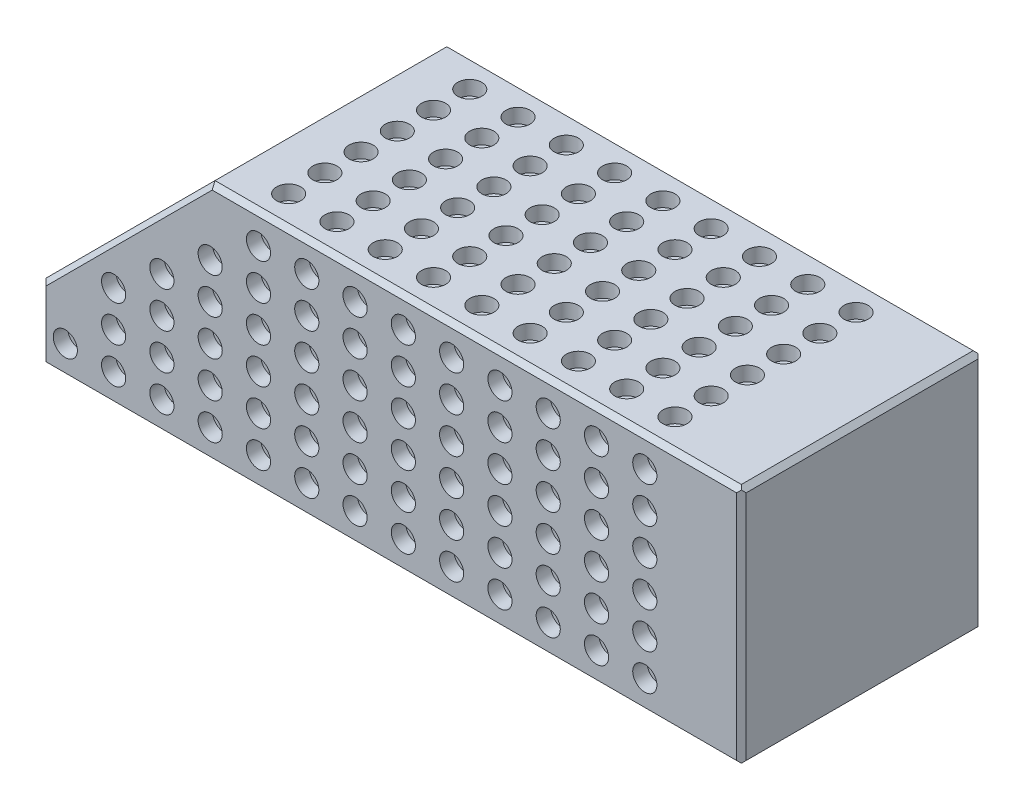
SolidWorks part; units mm, degrees
material "K110"
ref_plane "Front Plane" through (0, 0, 0) normal (0, 0, 1) x (1, 0, 0)
ref_plane "Top Plane" through (0, 0, 0) normal (0, 1, 0) x (1, 0, 0)
ref_plane "Right Plane" through (0, 0, 0) normal (1, 0, 0) x (0, 0, -1)
sketch "Sketch1" plane through (0, 0, 0) normal (0, 0, 1) x (1, 0, 0)
  line L1 (-72.5, -25) -> (72.5, -25)
  line L2 (-72.5, -25) -> (-72.5, 25)
  line L3 (-72.5, 25) -> (72.5, 25)
  line L4 (72.5, -25) -> (72.5, 25)
  line L5 (-72.5, -25) -> (72.5, 25) construction
  line L6 (-72.5, 25) -> (72.5, -25) construction
  point P0 (0, 0)
  dimension "D1" = 50
  dimension "D2" = 145
extrude "Boss-Extrude1" add sketch "Sketch1" along normal mid plane 50
sketch "Sketch2" plane through (0, 0, 0) normal (0, 0, 1) x (1, 0, 0)
  line L0 (-72.5, -10) -> (-37.5, 25)
  line L1 (-72.5, 25) -> (-72.5, -25) construction
  line L2 (72.5, 25) -> (-72.5, 25) construction
  line L3 (-37.5, 25) -> (-72.5, 25)
  line L4 (-72.5, 25) -> (-72.5, -10)
  dimension "D1" = 45
  dimension "D2" = 35
extrude "Cut-Extrude1" cut sketch "Sketch2" against normal through all both and the other way through all
hole_wizard "Ø12.0 (12) Diameter Hole1" positions "Sketch9" profile "Sketch4" hole size "Ø12.0" standard "ISO"
sketch "Sketch9" plane through (-72.5, 0, 0) normal (-1, 0, 0) x (0, 0, 1)
  line L0 (25, -25) -> (-25, -25) construction
  point P0 (0, -5)
  dimension "D1" = 20
sketch "Sketch4" plane through (-72.5, -5, 0) normal (0, 1, 0) x (0, 0, 1)
  line L0 (0, 0) -> (0, 20.5)
  line L1 (0, 20.5) -> (6, 20.5)
  line L2 (6, 20.5) -> (6, 0)
  line L5 (6, 0) -> (0, 0)
  line L10 (0, 20.5) -> (-6, 20.5) construction
  line L11 (0, -6.35) -> (0, 107.95) construction
  dimension "Hole Dia." = 12
  dimension "Hole Depth" = 20.5
  dimension "Drill Angle" = 180
hole_wizard "M10 Tapped Hole2" positions "Sketch12" profile "Sketch11" tap size "M10" standard "ISO"
sketch "Sketch12" plane through (-52, 0, 0) normal (-1, 0, 0) x (0, 0, 1)
  point P0 (0, -5)
sketch "Sketch11" plane through (-52, -5, 0) normal (0, 1, 0) x (0, 0, 1)
  line L0 (0, 0) -> (0, 27.5)
  line L1 (0, 27.5) -> (4.25, 24.9463)
  line L2 (4.25, 24.9463) -> (4.25, 0)
  line L5 (4.25, 0) -> (0, 0)
  line L10 (0, 27.5) -> (-4.25, 24.9463) construction
  line L11 (0, -6.35) -> (0, 107.95) construction
  dimension "Tap Drill Dia." = 8.5
  dimension "Tap Drill Depth" = 27.5
  dimension "Drill Angle" = 118
cosmetic thread "Hole Thread3" parameters "D1"=20, "D2"=10
chamfer "Chamfer1" distance 1 angle 45 10 edges at (-72.5, -17.5, -25) (0, -25, -25) (72.5, 0, -25) (17.5, 25, -25) (-55, 7.5, -25) (72.5, 0, 25) (0, -25, 25) (-72.5, -17.5, 25) (-55, 7.5, 25) (17.5, 25, 25)
chamfer "Chamfer2" distance 1 angle 45 2 edges at (72.5, -25, 0) (72.5, 25, 0)
chamfer "Chamfer3" distance 1 angle 45 1 edges at (-72.5, -25, 0)
sketch "Sketch13" plane through (0, -25, 0) normal (0, -1, 0) x (1, 0, 0)
  line L0 (71.5, -25) -> (-71.5, -25) construction
  line L1 (-72.5, -24) -> (-72.5, 24) construction
  circle A0 centre (-66.25, -18.75) radius 2.5
  dimension "D1" = 5
  dimension "D2" = 6.25
  dimension "D3" = 6.25
extrude "Cut-Extrude2" cut sketch "Sketch13" against normal blind 3
pattern_linear "LPattern1" count 6 spacing 7.5 along (0, 0, 1) count 13 spacing 10 along (1, 0, 0) of "Cut-Extrude2"
sketch "Sketch14" plane through (0, 0, 25) normal (0, 0, 1) x (1, 0, 0)
  line L0 (72.5, 24) -> (72.5, -24) construction
  line L1 (-37.5, 25) -> (71.5, 25) construction
  circle A0 centre (52.5, 18.75) radius 2.5
  dimension "D1" = 5
  dimension "D2" = 20
  dimension "D3" = 6.25
extrude "Cut-Extrude3" cut sketch "Sketch14" against normal blind 3
pattern_linear "LPattern2" count 6 spacing 7.5 along (0, -1, 0) count 13 spacing 10 along (-1, 0, 0) skipping (0, 9), (0, 10), (0, 11), (0, 12), (1, 10), (1, 11), (1, 12), (2, 11), (2, 12), (3, 12), (4, 12) of "Cut-Extrude3"
sketch "Sketch15" plane through (0, 25, 0) normal (0, 1, 0) x (1, 0, 0)
  line L0 (72.5, 24) -> (72.5, -24) construction
  line L1 (-37.0858, 25) -> (71.5, 25) construction
  circle A0 centre (52.5, 18.75) radius 2.5
  dimension "D1" = 5
  dimension "D2" = 20
  dimension "D3" = 6.25
extrude "Cut-Extrude4" cut sketch "Sketch15" against normal blind 3
pattern_linear "LPattern3" count 6 spacing 7.5 along (0, 0, 1) count 9 spacing 10 along (-1, 0, 0) of "Cut-Extrude4"
sketch "Sketch16" plane through (0, 0, -25) normal (0, 0, -1) x (-1, 0, 0)
  line L0 (-72.5, -24) -> (-72.5, 24) construction
  line L1 (-71.5, 25) -> (37.5, 25) construction
  circle A0 centre (-52.5, 18.75) radius 2.5
  dimension "D1" = 5
  dimension "D2" = 20
  dimension "D3" = 6.25
extrude "Cut-Extrude5" cut sketch "Sketch16" against normal blind 3
pattern_linear "LPattern4" count 13 spacing 10 along (-1, 0, 0) count 6 spacing 7.5 along (0, -1, 0) skipping (9, 0), (10, 0), (10, 1), (11, 0), (11, 1), (11, 2), (12, 0), (12, 1), (12, 2), (12, 3), (12, 4) of "Cut-Extrude5"
sketch "Sketch17" plane through (-31.25, 31.25, 0) normal (-0.7071, 0.7071, 0) x (0, 0, 1)
  line L0 (-25, -57.9221) -> (-25, -9.253) construction
  line L1 (-24, -8.8388) -> (24, -8.8388) construction
  circle A0 centre (-18.75, -16.3388) radius 2.5
  dimension "D1" = 5
  dimension "D2" = 6.25
  dimension "D3" = 7.5
extrude "Cut-Extrude6" cut sketch "Sketch17" against normal blind 3
pattern_linear "LPattern5" count 6 spacing 7.5 along (0, 0, 1) count 6 spacing 7.5 along (-0.7071, -0.7071, 0) skipping (2, 0), (2, 1), (2, 2), (2, 3), (2, 4), (2, 5), (3, 0), (3, 1), (3, 2), (3, 3), (3, 4), (3, 5) of "Cut-Extrude6"
